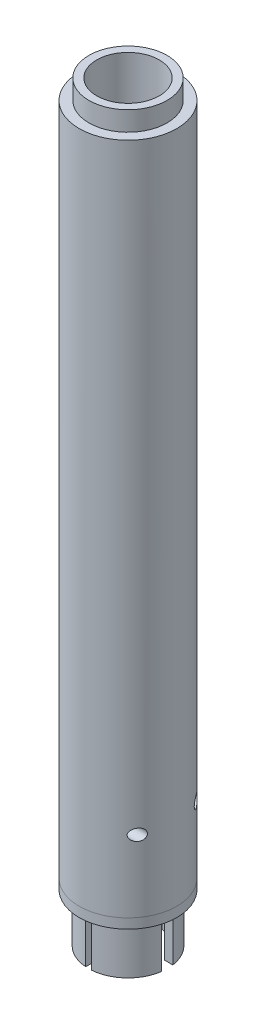
SolidWorks part; units mm, degrees
ref_plane "Front Plane" through (0, 0, 0) normal (0, 0, 1) x (1, 0, 0)
ref_plane "Top Plane" through (0, 0, 0) normal (0, 1, 0) x (1, 0, 0)
ref_plane "Right Plane" through (0, 0, 0) normal (1, 0, 0) x (0, 0, -1)
sketch "Sketch1" plane through (0, 0, 0) normal (0, 1, 0) x (1, 0, 0)
  circle A0 centre (0, 0) radius 12.7
  dimension "D1" = 25.4
extrude "Boss-Extrude1" add sketch "Sketch1" along normal blind 177.8
sketch "Sketch4" plane through (0, 177.8, 0) normal (0, 1, 0) x (1, 0, 0)
  circle A2 centre (0, 0) radius 10.16
  circle A3 centre (0, 0) radius 10.16
  dimension "D1" = 2.54
extrude "Boss-Extrude2" add sketch "Sketch4" along normal blind 5.08
sketch "Sketch5" plane through (0, 182.88, 0) normal (0, 1, 0) x (1, 0, 0)
  circle A0 centre (0, 0) radius 10.16 construction
  circle A1 centre (0, 0) radius 10.16 construction
  circle A2 centre (0, 0) radius 8.128
  dimension "D1" = 2.032
extrude "Cut-Extrude1" cut sketch "Sketch5" against normal through all
sketch "Sketch6" plane through (0, 0, 0) normal (0, -1, 0) x (1, 0, 0)
  circle A0 centre (0, 0) radius 10.287
  circle A1 centre (0, 0) radius 8.128 construction
  circle A2 centre (0, 0) radius 8.128
  dimension "D1" = 20.574
extrude "Boss-Extrude3" add sketch "Sketch6" along normal blind 12.7
sketch "Sketch7" plane through (0, -12.7, 0) normal (0, -1, 0) x (1, 0, 0)
  circle A0 centre (0, 0) radius 12.7 construction
  circle A1 centre (0, 0) radius 12.7
sketch "Sketch8" plane through (0, 182.88, 0) normal (0, 1, 0) x (1, 0, 0)
  circle A0 centre (0, 0) radius 12.7 construction
  circle A1 centre (0, 0) radius 12.7
ref_plane "Plane1" through (0, 2.54, 0) normal (0, -1, 0) x (-1, 0, 0)
split "Split1" trim tools "Plane1" bodies to split 104 resulting bodies 112 113
sketch "Sketch9" plane through (0, 0, 0) normal (1, 0, 0) x (0, 0, -1)
  line L0 (0, 23.749) -> (0, 21.1836) construction
  line L1 (-10.414, 23.749) -> (10.414, 23.749)
  line L2 (-10.414, 23.749) -> (-10.414, -35.56)
  line L3 (-10.414, -35.56) -> (10.414, -35.56)
  line L4 (10.414, 23.749) -> (10.414, -35.56)
  line L5 (-7.5946, 21.1836) -> (7.5946, 21.1836) construction
  circle A0 centre (-7.5946, 21.1836) radius 1.5
  circle A1 centre (7.5946, 21.1836) radius 1.5
  point P4 (0, 23.749)
  point P10 (0, 21.1836)
  dimension "D5" = 3
  dimension "D1" = 20.828
  dimension "D2" = 59.309
  dimension "D3" = 2.5654
  dimension "D4" = 15.1892
  dimension "D6" = 35.56
sketch "Sketch10" plane through (0, 0, 0) normal (1, 0, 0) x (0, 0, -1)
  line L4 (10.414, 23.749) -> (-10.414, 23.749)
  line L5 (10.414, -35.56) -> (10.414, 23.749)
  line L6 (-10.414, -35.56) -> (10.414, -35.56)
  line L7 (-10.414, 23.749) -> (-10.414, -35.56)
  line L8 (10.414, 23.749) -> (-10.414, 23.749)
  line L9 (10.414, -35.56) -> (10.414, 23.749)
  line L10 (-10.414, -35.56) -> (10.414, -35.56)
  line L11 (-10.414, 23.749) -> (-10.414, -35.56)
  circle A1 centre (7.5946, 21.1836) radius 1.5
  circle A2 centre (7.5946, 21.1836) radius 1.5
  circle A3 centre (-7.5946, 21.1836) radius 1.5
  circle A4 centre (-7.5946, 21.1836) radius 1.5
  dimension "D1" = 0
  dimension "D2" = 0
  dimension "D3" = 0
extrude "Cut-Extrude2" cut sketch "Sketch10" against normal blind 0.762 and the other way blind 0.762
sketch "Sketch11" plane through (0, 0, 0) normal (1, 0, 0) x (0, 0, -1)
  circle A0 centre (7.5946, 21.1836) radius 1.5 construction
  circle A1 centre (-7.5946, 21.1836) radius 1.5 construction
  circle A2 centre (7.5946, 21.1836) radius 1.5
  circle A3 centre (-7.5946, 21.1836) radius 1.5
extrude "Cut-Extrude3" cut sketch "Sketch11" against normal through all both and the other way through all
sketch "Sketch12" plane through (0, -12.7, 0) normal (0, -1, 0) x (1, 0, 0)
  line L1 (-25.4, 1.5) -> (25.4, 1.5)
  line L2 (-25.4, 1.5) -> (-25.4, -1.5)
  line L3 (-25.4, -1.5) -> (25.4, -1.5)
  line L4 (25.4, 1.5) -> (25.4, -1.5)
  point P4 (25.4, 0)
  point P6 (0, 1.5)
  point P7 (0, 0)
  dimension "D1" = 3
  dimension "D2" = 50.8
extrude "Cut-Extrude4" cut sketch "Sketch12" against normal up to surface (12.7 mm away) and the other way through all up to face at (0, 0, 12.7)
